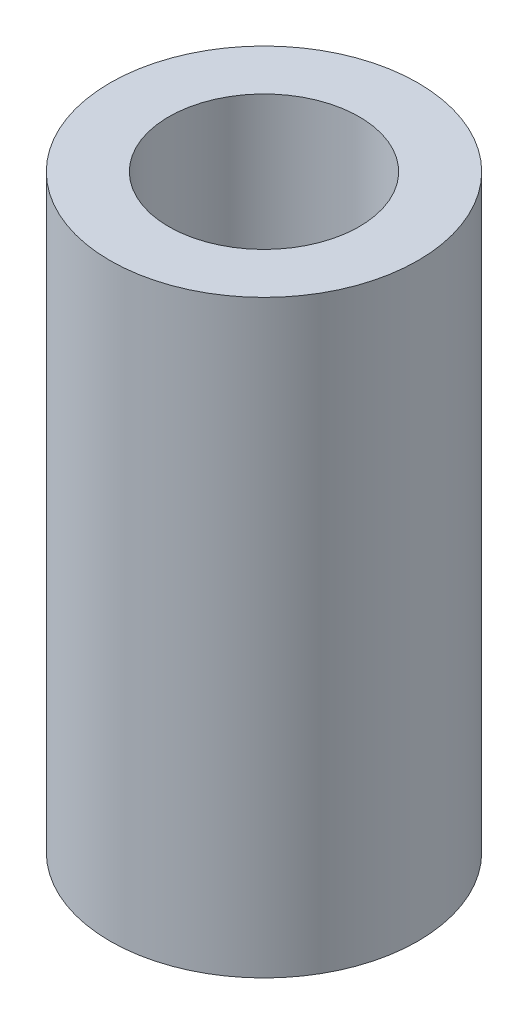
SolidWorks part; units mm, degrees
ref_plane "Front Plane" through (0, 0, 0) normal (0, 0, 1) x (1, 0, 0)
ref_plane "Top Plane" through (0, 0, 0) normal (0, 1, 0) x (1, 0, 0)
ref_plane "Right Plane" through (0, 0, 0) normal (1, 0, 0) x (0, 0, -1)
sketch "Sketch1" plane through (0, 0, 0) normal (0, 1, 0) x (1, 0, 0)
  circle A0 centre (0, 0) radius 4.445
  circle A1 centre (0, 0) radius 2.75
  dimension "D1" = 8.89
  dimension "D2" = 5.5
extrude "Boss-Extrude1" add sketch "Sketch1" along normal blind 17.018 contours A1 | A0 A1 region at (-4.3193, 0, 0) region at (0, 0, 0)
extrude "Cut-Extrude1" cut sketch "Sketch1<3>" along normal through all contours A1 region at (0, 0, 0)
sketch "Sketch1<3>" plane through (0, 0, 0) normal (0, 1, 0) x (1, 0, 0) same geometry as "Sketch1"
